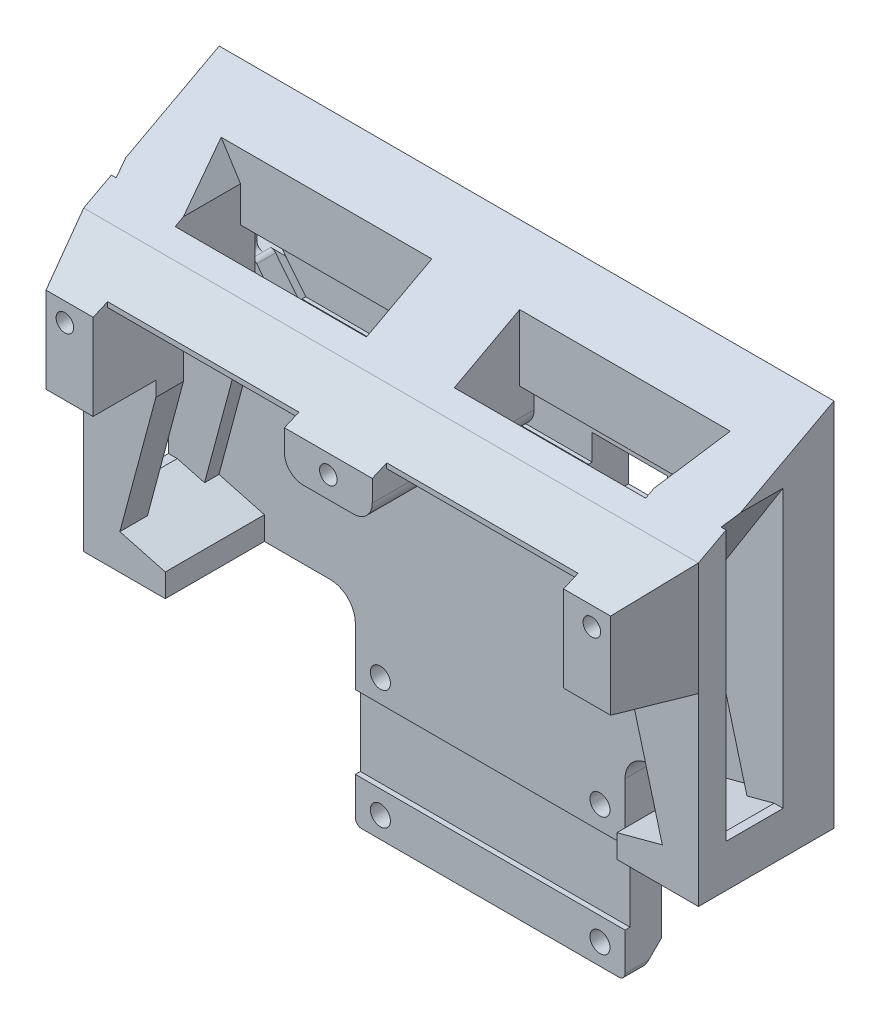
SolidWorks part; units mm, degrees
material "ABS"
ref_plane "Спереди" through (0, 0, 0) normal (0, 0, 1) x (1, 0, 0)
ref_plane "Сверху" through (0, 0, 0) normal (0, 1, 0) x (1, 0, 0)
ref_plane "Справа" through (0, 0, 0) normal (1, 0, 0) x (0, 0, -1)
sketch "Эскиз1" plane through (0, 0, 0) normal (0, 0, 1) x (1, 0, 0)
  line L0 (0, 0) -> (0, 112.9886) construction
  line L1 (21.5, 0) -> (-21.5, 0)
  line L2 (-21.5, 0) -> (-21.5, 32.9)
  line L3 (-25.5, 36.9) -> (-49, 36.9)
  line L4 (21.5, 0) -> (21.5, 32.9)
  line L5 (25.5, 36.9) -> (49, 36.9)
  line L6 (49, 36.9) -> (49, 98.9)
  line L7 (49, 98.9) -> (0, 98.9)
  line L8 (-49, 36.9) -> (-49, 98.9)
  line L9 (-49, 98.9) -> (0, 98.9)
  arc A0 (21.5, 32.9) -> (25.5, 36.9) centre (25.5, 32.9) cw
  arc A1 (-21.5, 32.9) -> (-25.5, 36.9) centre (-25.5, 32.9) ccw
  point P14 (21.5, 36.9)
  point P17 (-21.5, 36.9)
  dimension "D5" = 4
  dimension "D1" = 43
  dimension "D2" = 98
  dimension "D3" = 98.9
  dimension "D4" = 62
extrude "Бобышка-Вытянуть1" add sketch "Эскиз1" along normal blind 10
sketch "Эскиз11" plane through (0, 0, 10) normal (0, 0, 1) x (1, 0, 0)
  line L2 (21.5532, 42.9) -> (-21.5532, 42.9)
  line L4 (-16, 34.55) -> (16, 34.55)
  line L5 (16, 34.55) -> (16, 39.55)
  line L6 (16, 39.55) -> (21.5532, 39.55)
  line L8 (-16, 39.55) -> (-21.5532, 39.55)
  line L9 (-16, 34.55) -> (-16, 39.55)
  line L10 (21.5532, 39.55) -> (21.5532, 42.9)
  line L12 (-21.5532, 39.55) -> (-21.5532, 42.9)
  point P12 (0, 42.9)
  point P19 (0, 34.55)
  dimension "D1" = 8.35
  dimension "D3" = 5
extrude "Бобышка-Вытянуть7" add sketch "Эскиз11" along normal blind 11.6
fillet "Скругление4" radius 4 2 edges at (21.5, 0, 5) (-21.5, 0, 5)
sketch "Эскиз15" plane through (-49, 0, 0) normal (-1, 0, 0) x (0, 0, 1)
  line L0 (10, 92.1549) -> (21.6, 84.3306)
  line L1 (10, 39.4) -> (21.6, 39.4)
  line L2 (21.6, 39.4) -> (21.6, 84.3306)
  line L3 (10, 39.4) -> (10, 92.1549)
  dimension "D1" = 11.6
  dimension "D2" = 6.7451
  dimension "D3" = 39.4
  dimension "D4" = 10
  dimension "D5" = 44.9306
extrude "Бобышка-Вытянуть12" add sketch "Эскиз15" against normal up to surface (98 mm away) up to face at (49, 67.9, 5)
sketch "Эскиз16" plane through (-49, 0, 0) normal (-1, 0, 0) x (0, 0, 1)
  line L0 (0, 98.9) -> (10, 92.1549)
  line L1 (10, 92.1549) -> (12.1303, 92.1549)
  line L2 (12.1303, 92.1549) -> (12.1303, 101.596)
  line L3 (12.1303, 101.596) -> (0, 101.596)
  line L4 (0, 101.596) -> (0, 98.9)
extrude "Вырез-Вытянуть1" cut sketch "Эскиз16" against normal up to surface (98 mm away) up to face at (49, 65.8607, 10.4)
sketch "Эскиз14" plane through (0, 0, 10) normal (0, 0, 1) x (1, 0, 0)
  line L0 (37.5, 74.6823) -> (37.5, 86.6823)
  line L1 (37.5, 86.6823) -> (51.449, 108.7805)
  line L2 (37.5, 74.6823) -> (7, 74.6823)
  line L3 (39.6874, 73.1604) -> (27.2641, 73.1604)
  line L4 (-35.9903, 40.5938) -> (-27.2641, 73.1604)
  line L6 (7, 86.6823) -> (7, 108.7805)
  line L7 (-7, 108.7805) -> (-51.449, 108.7805)
  line L8 (-7, 86.6823) -> (-37.5, 86.6823)
  line L9 (-39.6874, 73.1604) -> (-27.2641, 73.1604)
  line L13 (-7, 74.6823) -> (-7, 86.6823)
  line L14 (7, 74.6823) -> (7, 86.6823)
  line L16 (0, 98.9) -> (0, -52.5147) construction
  line L19 (-49, 39.4) -> (-49, 36.9) construction
  line L20 (-16, 4.75) -> (-20.5, 4.75) construction
  line L21 (7, 86.6823) -> (37.5, 86.6823)
  line L22 (-47.5814, 43.6996) -> (-39.6874, 73.1604)
  line L25 (-35.9903, 40.5938) -> (-47.5814, 43.6996)
  line L26 (-7, 86.6823) -> (-7, 108.7805)
  line L27 (-37.5, 74.6823) -> (-7, 74.6823)
  line L28 (-37.5, 86.6823) -> (-51.449, 108.7805)
  line L29 (-37.5, 74.6823) -> (-37.5, 86.6823)
  line L34 (35.9903, 40.5938) -> (27.2641, 73.1604)
  line L36 (47.5814, 43.6996) -> (39.6874, 73.1604)
  line L37 (47.5814, 43.6996) -> (35.9903, 40.5938)
  line L38 (-39.6874, 73.1604) -> (-53.0045, 94.2575)
  line L39 (-47.5814, 43.6996) -> (-53.0045, 43.6996)
  line L40 (-53.0045, 94.2575) -> (-53.0045, 43.6996)
  line L45 (7, 108.7805) -> (51.449, 108.7805)
  line L47 (47.5814, 43.6996) -> (53.0045, 43.6996)
  line L48 (53.0045, 94.2575) -> (53.0045, 43.6996)
  line L49 (39.6874, 73.1604) -> (53.0045, 94.2575)
  dimension "D2" = 30.5
  dimension "D3" = 12
  dimension "D4" = 14
extrude "Вырез-Вытянуть2" cut sketch "Эскиз14" along normal blind 7.2 contours L38 L40 L39 L22 | L45 | L49 L36 L47 L48 | L8 | L25 L22 | L37 L36 L34 | L21 L14 L2 L0 | L29 L27 L13 L8 region at (22.25, 80.6823, 10) region at (25.9536, 98.4169, 10) region at (37.5306, 57.6406, 10) region at (48.2188, 67.1404, 10) region at (-37.5306, 57.6406, 10) region at (-48.2188, 67.1404, 10) region at (-25.9536, 98.4169, 10) region at (-22.25, 80.6823, 10)
extrude "Вырез-Вытянуть3" cut sketch "Эскиз14" against normal blind 1.9 contours L38 L40 L39 L22 | L45 | L49 L36 L47 L48 | L8 | L25 L22 | L37 L36 L34 | L21 L14 L2 L0 | L29 L27 L13 L8 region at (22.25, 80.6823, 10) region at (25.9536, 98.4169, 10) region at (37.5306, 57.6406, 10) region at (48.2188, 67.1404, 10) region at (-37.5306, 57.6406, 10) region at (-48.2188, 67.1404, 10) region at (-25.9536, 98.4169, 10) region at (-22.25, 80.6823, 10)
sketch "Эскиз18" plane through (0, 0, 8.1) normal (0, 0, 1) x (1, 0, 0)
  line L0 (7, 81) -> (37.5, 81)
  line L1 (7, 74.6823) -> (7, 93.4365) construction
  line L2 (37.5, 74.6823) -> (37.5, 86.6823) construction
  line L3 (37.5, 81) -> (37.5, 63.9372)
  line L4 (-35.9903, 40.5938) -> (-35.9903, 33.4321)
  line L5 (7, 73.58) -> (7, 81)
  line L6 (0, 0) -> (0, 113.6728) construction
  line L7 (-35.9903, 33.4321) -> (-16, 33.4321)
  line L8 (-17.5, 0) -> (17.5, 0) construction
  line L9 (-7, 73.58) -> (-7, 81)
  line L10 (-16, 39.4) -> (-16, 34.55) construction
  line L11 (-37.5, 81) -> (-37.5, 63.9372)
  line L12 (-7, 81) -> (-37.5, 81)
  line L13 (-37.5, 63.9372) -> (-43.2347, 42.535)
  line L15 (-35.9903, 40.5938) -> (-47.5814, 43.6996) construction
  line L16 (-16, 33.4321) -> (-16, 42.55)
  line L17 (-7, 73.58) -> (7, 73.58)
  line L18 (-16, 42.55) -> (16, 42.55)
  line L19 (-43.2347, 42.535) -> (-35.9903, 40.5938)
  line L20 (37.5, 63.9372) -> (43.2347, 42.535)
  line L21 (35.9903, 40.5938) -> (35.9903, 33.4321)
  line L22 (43.2347, 42.535) -> (35.9903, 40.5938)
  line L23 (35.9903, 33.4321) -> (16, 33.4321)
  line L24 (16, 33.4321) -> (16, 42.55)
  line L25 (-16, 34.55) -> (16, 34.55) construction
  point P29 (0, 40.5938)
  point P32 (0, 42.55)
  dimension "D1" = 8
  dimension "D2" = 81
extrude "Вырез-Вытянуть4" cut sketch "Эскиз18" against normal blind 2.3
extrude "Вырез-Вытянуть5" cut sketch "Эскиз18" along normal blind 35
sketch "Эскиз19" plane through (0, 0, 5.8) normal (0, 0, 1) x (1, 0, 0)
  line L0 (34.9411, 56.1006) -> (56.3747, 61.8438) construction
  line L1 (7, 73.58) -> (37.5, 73.58) construction
  line L2 (37.5, 63.9372) -> (37.5, 81) construction
  line L3 (38.8881, 41.3703) -> (30.9941, 70.831) construction
  line L4 (35.9903, 40.5938) -> (43.2347, 42.535) construction
  line L5 (32.4222, 61.6374) -> (34.3541, 62.155)
  line L7 (35.5281, 50.0463) -> (37.4599, 50.5639)
  line L8 (37.4599, 50.5639) -> (34.3541, 62.155)
  line L9 (32.4222, 61.6374) -> (25.1778, 59.6962)
  line L10 (25.1778, 59.6962) -> (28.2836, 48.1051)
  line L11 (7, 76.58) -> (37.5, 76.58) construction
  line L12 (7, 81) -> (7, 73.58) construction
  line L13 (37.5, 81) -> (37.5, 63.9372) construction
  line L14 (35.5281, 50.0463) -> (28.2836, 48.1051)
  line L17 (16.25, 78.08) -> (28.25, 78.08)
  line L21 (16.25, 78.08) -> (16.25, 68.08)
  line L22 (16.25, 68.08) -> (28.25, 68.08)
  line L23 (28.25, 68.08) -> (28.25, 78.08)
  point P19 (35.907, 56.3595)
  dimension "D1" = 12
  dimension "D2" = 1
  dimension "D3" = 3
  dimension "D4" = 12
  dimension "D5" = 9.25
  dimension "D6" = 2
  dimension "D7" = 12
  dimension "D8" = 9.5
  dimension "D9" = 10
  dimension "D10" = 1.5
extrude "Вырез-Вытянуть6" cut sketch "Эскиз19" against normal blind 10
sketch "Эскиз20" plane through (-49, 0, 0) normal (-1, 0, 0) x (0, 0, 1)
  line L0 (21.6, 39.4) -> (21.6, 84.3306) construction
  line L1 (0, 98.9) -> (0, 36.9) construction
  line L2 (0, 95.9) -> (21.6, 84.3306)
  line L3 (16.2881, 87.9135) -> (0, 98.9) construction
  line L4 (21.6, 84.3306) -> (21.6, 100.6471)
  line L5 (21.6, 100.6471) -> (-4.2921, 100.6471)
  line L6 (-4.2921, 100.6471) -> (-4.2921, 95.9)
  line L7 (-4.2921, 95.9) -> (0, 95.9)
  dimension "D1" = 3
extrude "Вырез-Вытянуть9" cut sketch "Эскиз20" against normal up to surface (98 mm away) up to face at (49, 62.3959, 11.8262)
sketch "Эскиз21" plane through (0, 0, 0) normal (0, 0, -1) x (-1, 0, 0)
  line L0 (0, 0) -> (0, 115.6505) construction
  line L1 (17.5, 0) -> (-17.5, 0) construction
  line L2 (0, 0) -> (84.712, 0) construction
  line L3 (35, 75) -> (46, 75)
  line L4 (35, 75) -> (35, 91)
  line L5 (35, 91) -> (46, 91)
  line L6 (46, 75) -> (46, 91)
  line L7 (-46, 75) -> (-46, 91)
  line L8 (-35, 91) -> (-46, 91)
  line L9 (-35, 75) -> (-35, 91)
  line L10 (-35, 75) -> (-46, 75)
  dimension "D1" = 16
  dimension "D2" = 11
  dimension "D3" = 35
  dimension "D4" = 75
extrude "Вырез-Вытянуть10" cut sketch "Эскиз21" against normal blind 4
sketch "Эскиз22" plane through (0, 0, 4) normal (0, 0, -1) x (-1, 0, 0)
  line L0 (0, 0) -> (0, 112.1332) construction
  line L1 (17.5, 0) -> (-17.5, 0) construction
  line L2 (39, 75) -> (39, 81)
  line L3 (-35, 75) -> (-39, 75)
  line L4 (-35, 75) -> (-35, 81)
  line L5 (-35, 81) -> (-39, 81)
  line L6 (-39, 75) -> (-39, 81)
  line L7 (35, 81) -> (39, 81)
  line L8 (35, 75) -> (35, 81)
  line L9 (35, 75) -> (39, 75)
  dimension "D1" = 4
  dimension "D2" = 6
extrude "Вырез-Вытянуть11" cut sketch "Эскиз22" against normal up to surface (1.8 mm away) up to face at (22.25, 73.08, 5.8)
sketch "Эскиз23" plane through (0, 0, 5.8) normal (0, 0, 1) x (1, 0, 0)
  line L0 (35, 81) -> (22.25, 65.0226)
  line L1 (37.5, 75) -> (26.7026, 61.4694)
  line L2 (22.25, 65.0226) -> (26.7026, 61.4694)
  line L3 (26.7026, 61.4694) -> (26.868, 61.5412)
  line L4 (37.5, 75) -> (35, 81)
  line L5 (0, 0) -> (0, 111.8495) construction
  line L6 (-17.5, 0) -> (17.5, 0) construction
  line L7 (-37.5, 75) -> (-35, 81)
  line L8 (-26.7026, 61.4694) -> (-26.868, 61.5412)
  line L9 (-22.25, 65.0226) -> (-26.7026, 61.4694)
  line L10 (-37.5, 75) -> (-26.7026, 61.4694)
  line L11 (-35, 81) -> (-22.25, 65.0226)
  line M1 (28.25, 78.08) -> (28.25, 68.08)
  line M2 (28.25, 68.08) -> (16.25, 68.08)
  line M9 (-35, 81) -> (-35, 75)
  line M10 (-35, 75) -> (-37.5, 75)
  line M28 (37.5, 75) -> (35, 75)
  line M29 (35, 75) -> (35, 81)
extrude "Вырез-Вытянуть12" cut sketch "Эскиз23" against normal blind 3 contours L0 L2 L1 M28 M29 M1 M2 | L11 L10 L9 M9 M10 region at (30.1461, 70.2718, 5.8) region at (-29.9013, 70.2158, 5.8)
fillet "Скругление5" radius 2 2 edges at (-24.4763, 63.246, 2.8) (24.4763, 63.246, 2.8)
sketch "Эскиз24" plane through (0, 0, 0) normal (0, 0, -1) x (-1, 0, 0)
  line L0 (0, 0) -> (0, 98.7235) construction
  line L1 (17.5, 0) -> (-17.5, 0) construction
  line L2 (-21.5, 4) -> (-21.5, 32.9) construction
  line L3 (-15.5, 3) -> (15.5, 3)
  line L4 (-18.5, 6) -> (-18.5, 27)
  line L5 (-15.5, 30) -> (15.5, 30)
  line L6 (18.5, 6) -> (18.5, 27)
  arc A0 (15.5, 3) -> (18.5, 6) centre (15.5, 6) ccw
  arc A1 (15.5, 30) -> (18.5, 27) centre (15.5, 27) cw
  arc A2 (-18.5, 27) -> (-15.5, 30) centre (-15.5, 27) cw
  arc A3 (-15.5, 3) -> (-18.5, 6) centre (-15.5, 6) cw
  point P12 (18.5, 3)
  point P16 (18.5, 30)
  dimension "D4" = 3
  dimension "D1" = 3
  dimension "D2" = 3
  dimension "D3" = 27
sketch "Эскиз25" plane through (0, 0, 21.6) normal (0, 0, 1) x (1, 0, 0)
  line L0 (0, 0) -> (0, 110.2009) construction
  line L1 (-17.5, 0) -> (17.5, 0) construction
  line L2 (-42, 77) -> (0, 77) construction
  circle A0 centre (-42, 77) radius 1.4
  circle A1 centre (0, 77) radius 1.4
  circle A2 centre (-11, 7.5) radius 1.5
  circle A3 centre (11, 7.5) radius 1.5
  circle A4 centre (42, 77) radius 1.4
  dimension "D1" = 2.8
  dimension "D4" = 2.8
  dimension "D5" = 11
  dimension "D7" = 3
  dimension "D2" = 42
  dimension "D3" = 77
  dimension "D6" = 7.5
extrude "Вырез-Вытянуть14" cut sketch "Эскиз25" against normal blind 5
fillet "Скругление7" radius 3 2 edges at (-7, 73.58, 13.7) (7, 73.58, 13.7)
fillet "Скругление8" radius 1 7 edges at (37.5, 75, 4.3) (39, 81, 4.9) (35, 75, 1.4) (46, 75, 2) (35, 91, 2) (46, 91, 2)
fillet "Скругление9" radius 1 9 edges at (-37.5, 75, 4.3) (-39, 81, 4.9) (-35, 75, 1.4) (-46, 75, 2) (-35, 91, 2) (-46, 91, 2)
ref_axis "Ось1" through (0, 77, 16.6) along (0, 0, 1)
sketch "Эскиз26" plane through (0, 0, 5.8) normal (0, 0, 1) x (1, 0, 0)
  line L1 (-28.7302, 50.2016) -> (28.5245, 50.2016)
  line L2 (-28.7302, 50.2016) -> (-28.7302, -10.4293)
  line L3 (-28.7302, -10.4293) -> (28.5245, -10.4293)
  line L4 (28.5245, 50.2016) -> (28.5245, -10.4293)
extrude "Вырез-Вытянуть15" cut sketch "Эскиз26" along normal blind 34
sketch "Эскиз27" plane through (-49, 0, 0) normal (-1, 0, 0) x (0, 0, 1)
  line L1 (-16.7698, 5) -> (21.9816, 5)
  line L2 (-16.7698, 5) -> (-16.7698, -13.1494)
  line L3 (-16.7698, -13.1494) -> (21.9816, -13.1494)
  line L4 (21.9816, 5) -> (21.9816, -13.1494)
  dimension "D1" = 5
extrude "Вырез-Вытянуть16" cut sketch "Эскиз27" against normal blind 90
sketch "Эскиз28" plane through (0, 0, 5.8) normal (0, 0, 1) x (1, 0, 0)
  line L0 (-21.5, 12) -> (21.5, 12)
  line L1 (-21.5, 5) -> (-21.5, 32.9) construction
  line L2 (21.5, 32.9) -> (21.5, 5) construction
  line L3 (-21.5, 23.7) -> (21.5, 23.7)
  line L4 (-21.5, 23.7) -> (-21.5, 12)
  line L5 (21.5, 23.7) -> (21.5, 12)
  line L7 (0, 0) -> (0, 31.4307) construction
  dimension "D1" = 12
  dimension "D2" = 11.7
extrude "Вырез-Вытянуть17" cut sketch "Эскиз28" against normal blind 0.8
sketch "Эскиз29" plane through (0, 0, 5.8) normal (0, 0, 1) x (1, 0, 0)
  line L0 (0, 0) -> (0, 35.6088) construction
  line L1 (-21.5, 17.85) -> (25.1961, 17.85) construction
  line L2 (-21.5, 23.7) -> (-21.5, 12) construction
  circle A0 centre (-17.5, 27.35) radius 1.6
  circle A1 centre (-17.5, 8.35) radius 1.6
  circle A2 centre (17.5, 8.35) radius 1.6
  circle A3 centre (17.5, 27.35) radius 1.6
  dimension "D3" = 3.2
  dimension "D1" = 19
  dimension "D2" = 17.5
extrude "Вырез-Вытянуть18" cut sketch "Эскиз29" against normal blind 10
sketch "Эскиз30" plane through (0, 0, 0) normal (0, 0, -1) x (-1, 0, 0)
  line L0 (-19.1, 4.0734) -> (-19.1, 5.426)
  line L1 (-17.5, 8.35) -> (-17.5, 12.3993) construction
  line L2 (0, 0) -> (0, 12.3993) construction
  line L3 (-15.9, 4.0734) -> (-15.9, 5.426)
  line L4 (19.1, 4.0734) -> (19.1, 5.426)
  line L5 (15.9, 4.0734) -> (15.9, 5.426)
  line L6 (-19.1, 4.0734) -> (-15.9, 4.0734)
  line L7 (15.9, 4.0734) -> (19.1, 4.0734)
  arc A0 (-15.6917, 5.8321) -> (-19.3083, 5.8321) centre (-17.5, 8.35) ccw
  circle A1 centre (-17.5, 27.35) radius 3.1
  arc A2 (19.3083, 5.8321) -> (15.6917, 5.8321) centre (17.5, 8.35) ccw
  circle A3 centre (17.5, 27.35) radius 3.1
  arc A4 (19.1, 5.426) -> (19.3083, 5.8321) centre (19.6, 5.426) cw
  arc A5 (15.9, 5.426) -> (15.6917, 5.8321) centre (15.4, 5.426) ccw
  arc A6 (-15.9, 5.426) -> (-15.6917, 5.8321) centre (-15.4, 5.426) cw
  arc A7 (-19.1, 5.426) -> (-19.3083, 5.8321) centre (-19.6, 5.426) ccw
  dimension "D1" = 6.2
  dimension "D2" = 6.2
  dimension "D3" = 6.2
  dimension "D4" = 6.2
  dimension "D6" = 0.5
  dimension "D5" = 1.6
extrude "Вырез-Вытянуть19" cut sketch "Эскиз30" against normal blind 3
sketch "Эскиз31" plane through (-21.5, 0, 0) normal (-1, 0, 0) x (0, 0, 1)
  line L0 (3, 5) -> (0, 8)
  line L1 (0, 5) -> (5.8, 5) construction
  line L2 (0, 32.9) -> (0, 5) construction
  line L3 (0, 8) -> (0, 5)
  line L4 (0, 5) -> (3, 5)
  dimension "D1" = 3
  dimension "D2" = 3
extrude "Вырез-Вытянуть20" cut sketch "Эскиз31" against normal up to surface (43 mm away) up to face at (21.5, 18.4, 4.15)
sketch "Эскиз32" plane through (0, 0, 21.6) normal (0, 0, 1) x (1, 0, 0)
  line L0 (-37.5, 66.304) -> (-49, 66.304)
  line L1 (-37.5, 74.8765) -> (-37.5, 63.9372) construction
  line L2 (-49, 39.4) -> (-49, 84.3306) construction
  line L3 (-49, 66.304) -> (-49, 84.3306)
  line L4 (-49, 84.3306) -> (49, 84.3306)
  line L5 (49, 84.3306) -> (49, 66.304)
  line L6 (49, 84.3306) -> (49, 39.4) construction
  line L7 (49, 66.304) -> (37.5, 66.304)
  line L8 (37.5, 81) -> (37.5, 63.9372) construction
  line L9 (37.5, 66.304) -> (37.5, 81)
  line L10 (37.5, 81) -> (7, 81)
  line L11 (7, 81) -> (7, 76.58)
  line L12 (4, 73.58) -> (-4, 73.58)
  line L13 (-7, 76.58) -> (-7, 81)
  line L14 (-7, 81) -> (-37.5, 81)
  line L15 (-37.5, 81) -> (-37.5, 66.304)
  line L16 (-37.5, 66.304) -> (-37.4742, 66.4718)
  arc A0 (7, 76.58) -> (4, 73.58) centre (4, 76.58) cw
  arc A1 (-4, 73.58) -> (-7, 76.58) centre (-4, 76.58) cw
  circle A2 centre (-42, 77) radius 1.4
  circle A3 centre (0, 77) radius 1.4
  circle A4 centre (42, 77) radius 1.4
  circle M1 centre (42, 77) radius 1.4
  circle M2 centre (0, 77) radius 1.4
  circle M3 centre (-42, 77) radius 1.4
  line M4 (-7, 81) -> (-7, 76.58)
  arc M5 (-7, 76.58) -> (-4, 73.58) centre (-4, 76.58) ccw
  line M6 (-4, 73.58) -> (4, 73.58)
  arc M7 (4, 73.58) -> (7, 76.58) centre (4, 76.58) ccw
  line M8 (7, 76.58) -> (7, 81)
  line M9 (7, 81) -> (37.5, 81)
  line M10 (37.5, 81) -> (37.5, 63.9372)
  line M17 (49, 39.4) -> (49, 84.3306)
  line M18 (49, 84.3306) -> (-49, 84.3306)
  line M19 (-49, 84.3306) -> (-49, 39.4)
  line M26 (-37.5, 63.9372) -> (-37.5, 81)
  line M27 (-37.5, 81) -> (-7, 81)
  dimension "D1" = 3
extrude "Бобышка-Вытянуть13" add sketch "Эскиз32" along normal blind 10 contours L7 L0 M17 M18 M19 M26 M27 M4 M5 M6 M7 M8 M9 M10 M2 M3 M1 region at (-43.25, 67.3005, 21.6)
sketch "Эскиз33" plane through (-49, 0, 0) normal (-1, 0, 0) x (0, 0, 1)
  line L0 (21.6, 84.3306) -> (31.6, 80.0006)
  line L1 (31.6, 84.3306) -> (31.6, 66.304) construction
  line L2 (31.6, 80.0006) -> (31.6, 84.3306)
  line L3 (31.6, 84.3306) -> (21.6, 84.3306)
  dimension "D1" = 4.33
extrude "Вырез-Вытянуть21" cut sketch "Эскиз33" against normal blind 105
sketch "Эскиз35" plane through (49, 0, 0) normal (1, 0, 0) x (0, 0, -1)
  line L0 (-21.6, 39.4) -> (-10, 39.4)
  line L1 (-10, 39.4) -> (-10, 36.9)
  line L2 (-10, 36.9) -> (-21.6, 36.9)
  line L3 (-21.6, 36.9) -> (-21.6, 39.4)
extrude "Бобышка-Вытянуть14" add sketch "Эскиз35" against normal up to surface (13.0097 mm away) up to face at (35.9903, 38.9646, 12.4667)
sketch "Эскиз36" plane through (-49, 0, 0) normal (-1, 0, 0) x (0, 0, 1)
  line L1 (10, 39.4) -> (21.6, 39.4)
  line L2 (10, 39.4) -> (10, 36.9)
  line L3 (10, 36.9) -> (21.6, 36.9)
  line L4 (21.6, 39.4) -> (21.6, 36.9)
extrude "Бобышка-Вытянуть15" add sketch "Эскиз36" against normal up to surface (13.0097 mm away) up to face at (-35.9903, 38.9646, 12.4667)
sketch "Эскиз37" plane through (0, 66.304, 0) normal (0, -1, 0) x (1, 0, 0)
  line L0 (49, 21.6) -> (45, 31.6)
  line L1 (49, 31.6) -> (49, 21.6) construction
  line L2 (49, 31.6) -> (37.5, 31.6) construction
  line L3 (45, 31.6) -> (49, 31.6)
  line L4 (49, 31.6) -> (49, 21.6)
  line L5 (0, 0) -> (0, 44.5067) construction
  line L6 (14.4198, 0) -> (-14.4198, 0) construction
  line L7 (-49, 31.6) -> (-49, 21.6)
  line L8 (-45, 31.6) -> (-49, 31.6)
  line L9 (-49, 21.6) -> (-45, 31.6)
  dimension "D1" = 4
extrude "Вырез-Вытянуть23" cut sketch "Эскиз37" against normal blind 22
fillet "Скругление10" radius 1 2 edges at (21.5, 5, 4.4) (-21.5, 5, 4.4)
sketch "Эскиз41" plane through (0, 0, 5.8) normal (0, 0, 1) x (1, 0, 0)
  line L0 (7, 81) -> (33.8318, 81)
  line L1 (35.4814, 81) -> (7, 81) construction
  line L2 (33.8318, 81) -> (33.8318, 80.2)
  line L3 (33.8318, 80.2) -> (7, 80.2)
  line L4 (7, 81) -> (7, 76.58) construction
  line L5 (7, 80.2) -> (7, 81)
  dimension "D1" = 0.8
extrude "Бобышка-Вытянуть16" add sketch "Эскиз41" along normal blind 0.4
ref_plane "Плоскость3" through (0, 81.7621, 5.187) normal (0, -0.998, -0.0633) x (-1, 0, 0)
sketch "Эскиз42" plane through (0, 81.7621, 5.187) normal (0, -0.998, -0.0633) x (-1, 0, 0)
  line L1 (-7, -26.6881) -> (-7, -0.9398) construction
  line L2 (-7, -8.4581) -> (-37.5, -8.4581)
  line L3 (-7, -8.4581) -> (-7, -13.0371)
  line L4 (-7, -13.0371) -> (-37.5, -13.0371)
  line L5 (-37.5, -8.4581) -> (-37.5, -13.0371)
  line L6 (-37.5, -24.1048) -> (-37.5, -12.0371) construction
  line L7 (-7, -12.0371) -> (-37.5, -12.0371) construction
  dimension "D1" = 1
extrude "Вырез-Вытянуть26" cut sketch "Эскиз42" against normal blind 12
ref_plane "Плоскость4" through (0, 0, 18.202) normal (0, 0, 1) x (1, 0, 0)
sketch "Эскиз43" plane through (0, 0, 18.202) normal (0, 0, 1) x (1, 0, 0)
  line L0 (37.5, 80.0006) -> (37.5, 66.304) construction
  line L1 (7, 81) -> (37.5, 81)
  line L2 (7, 81) -> (7, 80.2)
  line L3 (7, 80.2) -> (37.5, 80.2)
  line L4 (37.5, 81) -> (37.5, 80.2)
  dimension "D1" = 0.8
extrude "Бобышка-Вытянуть17" add sketch "Эскиз43" along normal up to vertex (11.0899 mm away) up to point (7, 81, 29.292)
mirror "Зеркальное отражение11" about plane through (0, 0, 0) normal (1, 0, 0) of "Бобышка-Вытянуть16"
mirror "Зеркальное отражение12" about plane through (0, 0, 0) normal (1, 0, 0) of "Вырез-Вытянуть26"
sketch "Эскиз44" plane through (0, 0, 18.202) normal (0, 0, 1) x (1, 0, 0)
  line L0 (-37.5, 66.304) -> (-37.5, 80.0006) construction
  line L1 (-7, 81) -> (-37.5, 81)
  line L2 (-7, 81) -> (-7, 80.2)
  line L3 (-7, 80.2) -> (-37.5, 80.2)
  line L4 (-37.5, 81) -> (-37.5, 80.2)
  dimension "D1" = 0.8
extrude "Бобышка-Вытянуть18" add sketch "Эскиз44" along normal up to vertex (11.0899 mm away) up to point (-37.5, 81, 29.292)
sketch "Эскиз45" plane through (0, 0, 0) normal (0, 0, -1) x (-1, 0, 0)
  line L0 (-36, 91) -> (-34, 91)
  line L1 (-33, 90) -> (-33, 76)
  line L2 (-34, 75) -> (-36, 75)
  line L3 (-35, 76) -> (-35, 90) construction
  line L4 (-36, 91) -> (-36, 75)
  line L5 (0, 0) -> (0, 108.3094) construction
  line L6 (36, 91) -> (36, 75)
  line L7 (34, 75) -> (36, 75)
  line L8 (33, 90) -> (33, 76)
  line L9 (36, 91) -> (34, 91)
  arc A0 (-33, 76) -> (-34, 75) centre (-34, 76) cw
  arc A1 (-34, 91) -> (-33, 90) centre (-34, 90) cw
  arc A2 (34, 91) -> (33, 90) centre (34, 90) ccw
  arc A3 (33, 76) -> (34, 75) centre (34, 76) ccw
  dimension "D2" = 1
  dimension "D1" = 2
extrude "Вырез-Вытянуть27" cut sketch "Эскиз45" against normal up to surface (4 mm away) up to face at (-39.2591, 82.3255, 4)
sketch "Эскиз46" plane through (0, 0, 5.8) normal (0, 0, 1) x (1, 0, 0)
  line L0 (-29.398, 73.98) -> (16.25, 73.98)
  line L2 (16.25, 78.08) -> (16.25, 68.08) construction
  line L3 (16.25, 73.98) -> (16.25, 73.18)
  line L4 (16.25, 73.18) -> (-28.7596, 73.18)
  line L6 (4, 73.58) -> (-4, 73.58) construction
  line L7 (-28.7596, 73.18) -> (-29.398, 73.98)
  line L8 (-33, 78.4937) -> (-23.4975, 66.5859) construction
  dimension "D1" = 0.4
  dimension "D2" = 0.8
extrude "Бобышка-Вытянуть19" add sketch "Эскиз46" along normal blind 0.6
